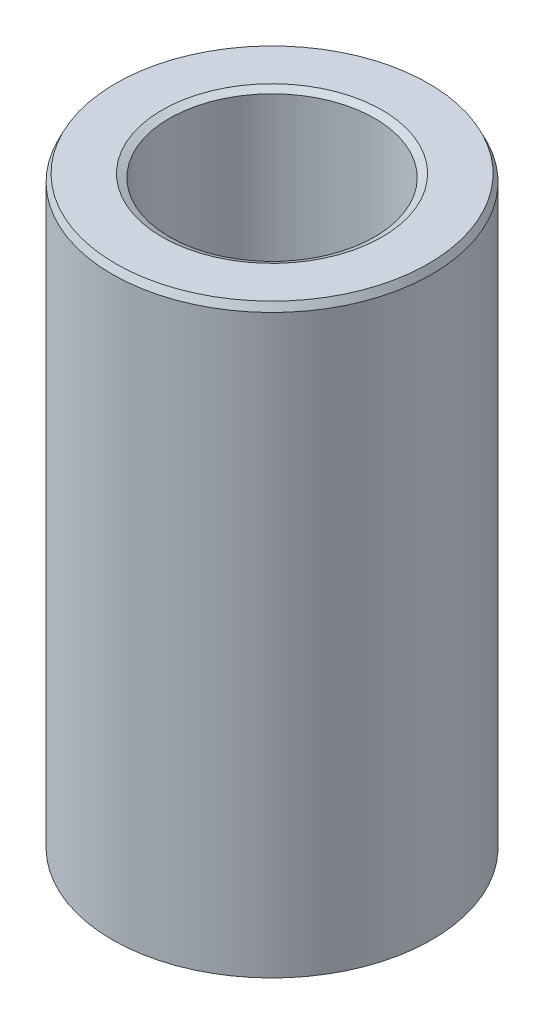
SolidWorks part; units mm, degrees
ref_plane "Front Plane" through (0, 0, 0) normal (0, 0, 1) x (1, 0, 0)
ref_plane "Top Plane" through (0, 0, 0) normal (0, 1, 0) x (1, 0, 0)
ref_plane "Right Plane" through (0, 0, 0) normal (1, 0, 0) x (0, 0, -1)
sketch "Sketch1" plane through (0, 0, 0) normal (0, 1, 0) x (1, 0, 0)
  circle A0 centre (0, 0) radius 52.5
  dimension "SLEEVE_OD" = 105
extrude "Boss-Extrude1" add sketch "Sketch1" along normal blind 192.9048
sketch "Sketch2" plane through (0, 0, 0) normal (0, 1, 0) x (1, 0, 0)
  circle A0 centre (0, 0) radius 33.7328
  dimension "BORE_D" = 67.4657
extrude "Cut-Extrude1" cut sketch "Sketch2" along normal through all
chamfer "Chamfer1" distance 2.4105 angle 25.576 4 edges at (0, 192.9048, 33.7328) (0, 0, 33.7328) (0, 0, 52.5) (0, 192.9048, 52.5) first distance on face at (0, 192.9048, 33.7328) first distance on face at (0, 0, 33.7328) first distance on face at (0, 192.9048, 52.5)
